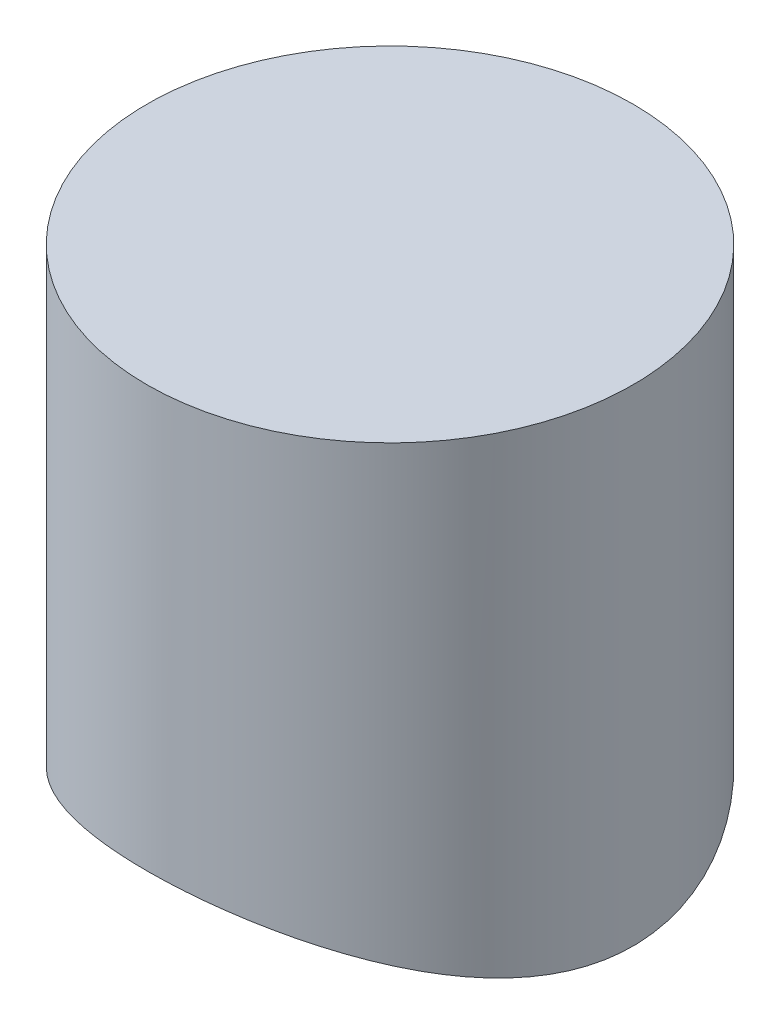
SolidWorks part; units mm, degrees
ref_plane "Front Plane" through (0, 0, 0) normal (0, 0, 1) x (1, 0, 0)
ref_plane "Top Plane" through (0, 0, 0) normal (0, 1, 0) x (1, 0, 0)
ref_plane "Right Plane" through (0, 0, 0) normal (1, 0, 0) x (0, 0, -1)
sketch "Sketch1" plane through (0, 0, 0) normal (0, 1, 0) x (1, 0, 0)
  circle A0 centre (0, 0) radius 20
  dimension "D1" = 40
extrude "Boss-Extrude1" add sketch "Sketch1" along normal blind 40
sketch "Sketch2" plane through (0, 0, 0) normal (0, -1, 0) x (1, 0, 0)
  circle A0 centre (0, 0) radius 10
  dimension "D1" = 20
extrude "Cut-Extrude1" cut sketch "Sketch2" against normal blind 25
thread "Thread1" pitch 4 method extrude profile "Thread Profile1" start angle 0, offset 0, length 0, pitch 4, diameter 20
ref_plane "Plane1" through (10, 0, 0) normal (0, 0, 1) x (1, 0, 0)
sketch "Thread Profile1" plane through (10, 0, 0) normal (0, 0, 1) x (1, 0, 0)
  line L0 (0, 0) -> (0, 4) construction
  line L11 (0, 0) -> (0, 3.5)
  line L12 (0, 3.5) -> (-2.1651, 2.25)
  line L13 (-2.1651, 2.25) -> (-2.1651, 1.25)
  line L15 (-2.1651, 1.25) -> (0, 0)
  line L17 (-2.1651, 1.75) -> (0, 1.75) construction
  point P2 (0, 0)
  dimension "Pitch" = 4
  dimension "Profile_Angle" = 60
  dimension "Profile_Land" = 1
  dimension "Profile_Height" = 2.1651
sketch "Sketch3" plane through (0, 0, 0) normal (0, 0, 1) x (1, 0, 0)
  circle A0 centre (0, -34.641) radius 40
  dimension "D1" = 80
extrude "Cut-Extrude2" cut sketch "Sketch3" against normal through all both and the other way through all
